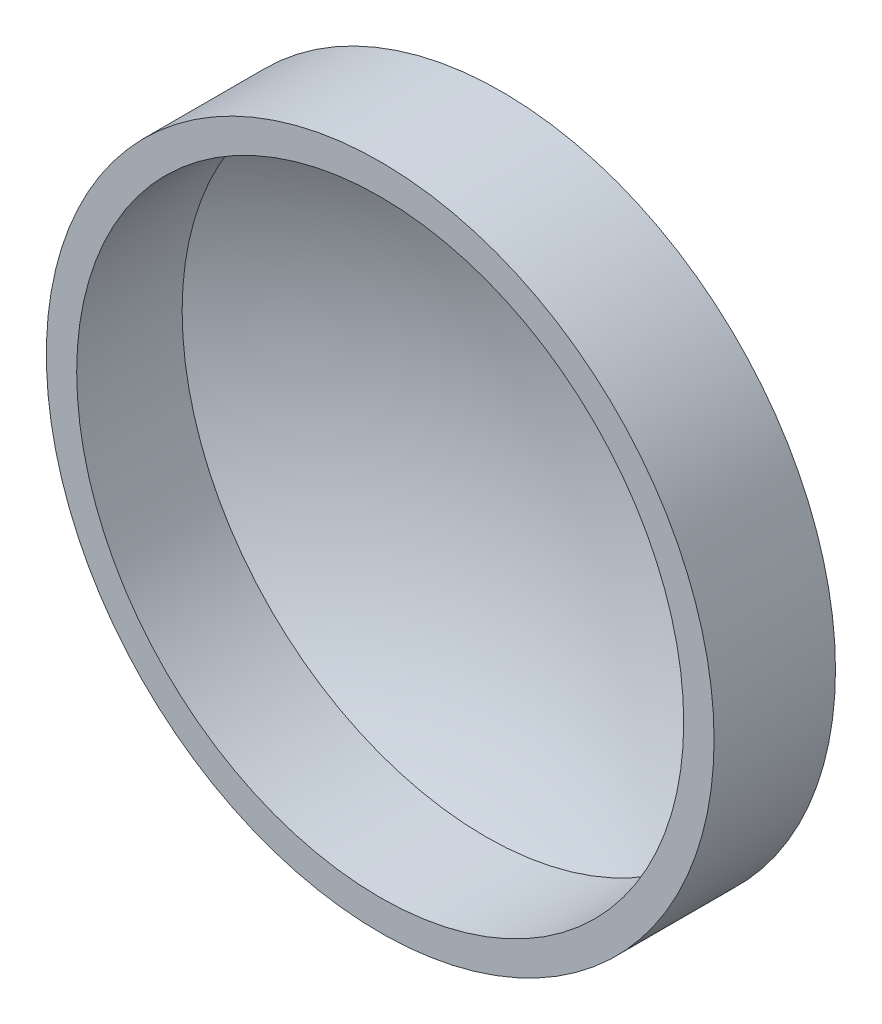
SolidWorks part; units mm, degrees
ref_plane "Front Plane" through (0, 0, 0) normal (0, 0, 1) x (1, 0, 0)
ref_plane "Top Plane" through (0, 0, 0) normal (0, 1, 0) x (1, 0, 0)
ref_plane "Right Plane" through (0, 0, 0) normal (1, 0, 0) x (0, 0, -1)
sketch "Sketch4" plane through (0, 0, 0) normal (0, 1, 0) x (1, 0, 0)
  line L0 (-125.4037, 0) -> (130.8958, 0) construction
  line L1 (0, 0) -> (0, 95.1207) construction
  line L2 (0, 29.718) -> (0, 10.668)
  line L3 (27.94, 10.668) -> (27.94, 20.828)
  line L4 (0, 10.668) -> (27.94, 10.668)
  arc A1 (0, 29.718) -> (27.94, 20.828) centre (0.0289, -18.542) cw
  dimension "D1" = 48.26
  dimension "D3" = 10.16
  dimension "D4" = 19.05
  dimension "D5" = 27.94
revolve "Revolve1" add sketch "Sketch4" angle 360 about L1
shell "Shell4" thickness 2.54 removed face at (27.94, 0, -10.668)
